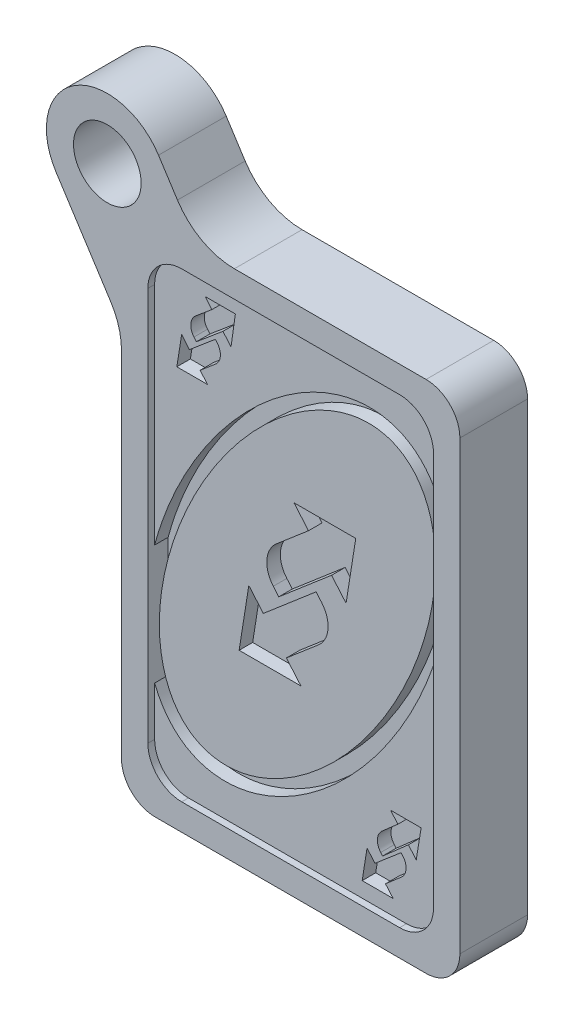
SolidWorks part; units mm, degrees
note: The reader was unsure of these and kept them because the rebuilt part matched: shared geometry of "Sketch1<3>", "Sketch1<4>".
ref_plane "Front Plane" through (0, 0, 0) normal (0, 0, 1) x (1, 0, 0)
ref_plane "Top Plane" through (0, 0, 0) normal (0, 1, 0) x (1, 0, 0)
ref_plane "Right Plane" through (0, 0, 0) normal (1, 0, 0) x (0, 0, -1)
sketch "Sketch1" plane through (0, 0, 0) normal (0, 0, 1) x (1, 0, 0)
  line L0 (11.3955, 51.9637) -> (56.9777, 51.9637) construction
  line L1 (0, 15.2) -> (10, 15.2)
  line L2 (0, 15.2) -> (0, 0)
  line L3 (0, 0) -> (10, 0)
  line L4 (10, 15.2) -> (10, 0)
  line L5 (0, 15.2) -> (10, 0) construction
  line L6 (2.3143, 5.3069) -> (7.6857, 9.8931) construction
  line L7 (5, 7.6) -> (8.0372, 12.7941) construction
  line L8 (9.22, 0.78) -> (0.78, 0.78)
  line L9 (9.22, 0.78) -> (9.22, 14.42)
  line L10 (9.22, 14.42) -> (0.78, 14.42)
  line L11 (0.78, 0.78) -> (0.78, 14.42)
  line L12 (8.2544, 13.1656) -> (8.0372, 12.7941) construction
  line L13 (4.4481, 7.2603) -> (6.0083, 8.5924)
  line L14 (4.4481, 7.2603) -> (4.2857, 7.4504)
  line L15 (4.3747, 8.5783) -> (5.3265, 9.3909)
  line L16 (5.3265, 9.3909) -> (4.8977, 9.8931)
  line L17 (4.8977, 9.8931) -> (6.7232, 9.8931)
  line L18 (6.7232, 9.8931) -> (6.437, 8.0902)
  line L19 (6.437, 8.0902) -> (6.0083, 8.5924)
  line L20 (5.5519, 7.9397) -> (3.9917, 6.6076)
  line L21 (5.5519, 7.9397) -> (5.7143, 7.7496)
  line L22 (5.6253, 6.6217) -> (4.6735, 5.8091)
  line L23 (4.6735, 5.8091) -> (5.1023, 5.3069)
  line L24 (5.1023, 5.3069) -> (3.2768, 5.3069)
  line L25 (3.2768, 5.3069) -> (3.563, 7.1098)
  line L26 (3.563, 7.1098) -> (3.9917, 6.6076)
  line L27 (2.0132, 12.5704) -> (2.7993, 13.2308)
  line L28 (2.7993, 13.2308) -> (3.0366, 12.9483)
  line L29 (3.0366, 12.9483) -> (3.166, 13.858)
  line L30 (3.166, 13.858) -> (2.2723, 13.858)
  line L31 (2.2723, 13.858) -> (2.4705, 13.6221)
  line L32 (2.4705, 13.6221) -> (1.9907, 13.219)
  line L33 (1.9418, 12.6554) -> (2.0132, 12.5704)
  line L34 (2.5735, 12.9128) -> (1.808, 12.2671)
  line L35 (1.808, 12.2671) -> (1.5787, 12.5388)
  line L36 (1.5787, 12.5388) -> (1.4363, 11.6412)
  line L37 (1.4363, 11.6412) -> (2.3413, 11.6412)
  line L38 (2.3413, 11.6412) -> (2.1251, 11.8976)
  line L39 (2.1251, 11.8976) -> (2.5817, 12.2827)
  line L40 (2.6295, 12.8464) -> (2.5735, 12.9128)
  line L41 (7.5174, 2.1621) -> (8.2777, 2.8289)
  line L42 (8.2777, 2.8289) -> (8.5108, 2.5632)
  line L43 (8.5108, 2.5632) -> (8.6547, 3.4521)
  line L44 (8.6547, 3.4521) -> (7.7511, 3.4521)
  line L45 (7.7511, 3.4521) -> (7.9693, 3.2033)
  line L46 (7.9693, 3.2033) -> (7.4984, 2.7903)
  line L47 (7.4615, 2.2259) -> (7.5174, 2.1621)
  line L48 (7.2917, 1.8634) -> (8.0634, 2.5212)
  line L49 (7.2917, 1.8634) -> (7.0562, 2.1357)
  line L50 (7.0562, 2.1357) -> (6.9127, 1.2305)
  line L51 (6.9127, 1.2305) -> (7.8289, 1.2305)
  line L52 (7.8289, 1.2305) -> (7.6012, 1.4938)
  line L53 (7.6012, 1.4938) -> (8.0714, 1.9004)
  line L54 (8.1123, 2.4647) -> (8.0634, 2.5212)
  arc A0 (4.2857, 7.4504) -> (4.3747, 8.5783) centre (4.8942, 7.9698) cw
  arc A1 (5.7143, 7.7496) -> (5.6253, 6.6217) centre (5.1058, 7.2302) cw
  arc A2 (1.9907, 13.219) -> (1.9418, 12.6554) centre (2.248, 12.9128) ccw
  arc A3 (2.5817, 12.2827) -> (2.6295, 12.8464) centre (2.3238, 12.5885) ccw
  arc A4 (7.4984, 2.7903) -> (7.4615, 2.2259) centre (7.7622, 2.4896) ccw
  arc A5 (8.0714, 1.9004) -> (8.1123, 2.4647) centre (7.8098, 2.203) ccw
  ellipse E0 centre (5, 7.6) end of major axis (1.9628, 2.4059) minor radius 3.1576
  ellipse E1 centre (5, 7.6) end of major axis (1.7456, 2.0344) minor radius 3.5876
  point P9 (5, 7.6)
  point P48 (5, 7.6)
  dimension "D12" = 0.8
  dimension "D18" = 0.4
  dimension "D19" = 0.4
  dimension "D20" = 0.4
  dimension "D21" = 0.4
  dimension "D1" = 10
  dimension "D2" = 15.2
  dimension "D3" = 0.78
  dimension "D4" = 0.78
  dimension "D5" = 0.78
  dimension "D6" = 0.78
  dimension "D7" = 3.1576
  dimension "D8" = 0.43
  dimension "D9" = 0.4304
  dimension "D10" = 97.15
  dimension "D11" = 0.1
  dimension "D13" = 1.05
  dimension "D14" = 1.8254
  dimension "D15" = 1.2515
  dimension "D16" = 0.6403
  dimension "D17" = 2
extrude "Boss-Extrude1" add sketch "Sketch1" along normal mid plane 0.8 contours L2 L3 L4 L1
extrude "Boss-Extrude2" add sketch "Sketch1<3>" along normal mid plane 1.6 contours L4 L1 L2 L3 E1 L11 L10 L9 L8 | E1 L9 L10 L11 A3 L39 L38 L37 L36 L35 L34 L40 A2 L32 L31 L30 L29 L28 L27 L33 | E0 L21 A1 L22 L23 L24 L25 L26 L20 L14 A0 L15 L16 L17 L18 L19 L13 | E1 L11 L8 L9 A4 L46 L45 L44 L43 L42 L41 L47 A5 L53 L52 L51 L50 L49 L48 L54
sketch "Sketch1<3>" plane through (0, 0, 0) normal (0, 0, 1) x (1, 0, 0) same geometry as "Sketch1"
extrude "Boss-Extrude3" add sketch "Sketch1<4>" along normal mid plane 2 contours L10 L11 L8 L9 | L1 L4 L3 L2
sketch "Sketch1<4>" plane through (0, 0, 0) normal (0, 0, 1) x (1, 0, 0) same geometry as "Sketch1"
fillet "Fillet1" radius 1 12 edges at (10, 15.2, 0) (10, 0, 0) (0, 0, 0) (0, 15.2, 0) (0.78, 14.42, -0.9) (0.78, 6.7512, -0.6) (9.22, 11.9805, -0.6) (9.22, 14.42, -0.9) (0.78, 0.78, 0.9) (9.22, 0.78, 0.9) (9.22, 14.42, 0.9) (0.78, 14.42, 0.9)
sketch "Sketch2" plane through (0, 0, 1) normal (0, 0, 1) x (1, 0, 0)
  line L0 (1, 15.2) -> (9, 15.2) construction
  line L1 (0, 12.038) -> (-1.9313, 15.036)
  line L2 (0, 14.2) -> (0, 1) construction
  line L3 (1.0951, 16.9856) -> (2.2454, 15.2)
  line L4 (-0.4181, 16.0108) -> (0.2929, 14.9071) construction
  line L5 (0.2929, 14.9071) -> (9.7071, 0.2929) construction
  line L6 (-1.9313, 15.036) -> (1.0951, 16.9856) construction
  circle A0 centre (-0.4181, 16.0108) radius 1
  arc A1 (1.0951, 16.9856) -> (-1.9313, 15.036) centre (-0.4181, 16.0108) ccw
  arc A4 (1, 15.2) -> (0, 14.2) centre (1, 14.2) ccw construction
  arc A6 (9, 0) -> (10, 1) centre (9, 1) ccw construction
  dimension "D2" = 2
  dimension "D3" = 0.8
  dimension "D1" = 0.3
extrude "Boss-Extrude4" add sketch "Sketch2" against normal up to surface (2 mm away)
fillet "Fillet2" radius 2 2 edges at (2.2454, 15.2, 0) (0, 12.038, 0)
